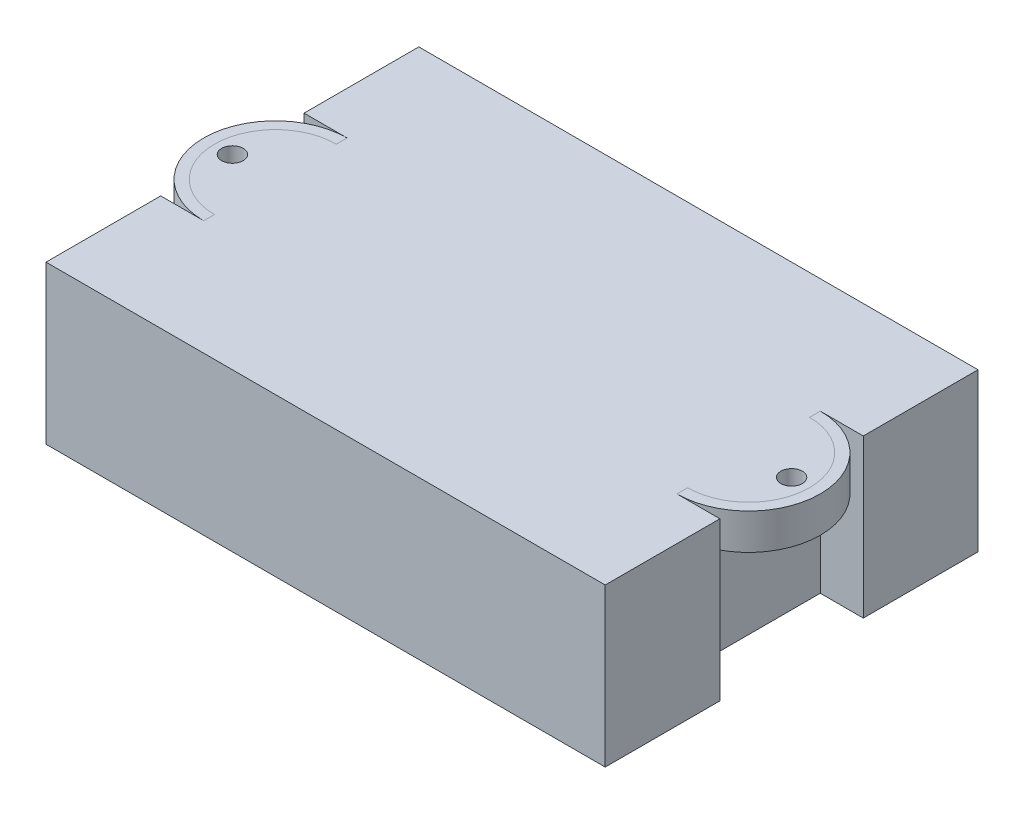
SolidWorks part; units mm, degrees
ref_plane "Piano frontale" through (0, 0, 0) normal (0, 0, 1) x (1, 0, 0)
ref_plane "Piano superiore" through (0, 0, 0) normal (0, 1, 0) x (1, 0, 0)
ref_plane "Piano destro" through (0, 0, 0) normal (1, 0, 0) x (0, 0, -1)
sketch "Schizzo1" plane through (0, 0, 0) normal (0, 1, 0) x (1, 0, 0)
  line L1 (-39, 26) -> (39, 26)
  line L2 (-39, 26) -> (-39, -26)
  line L3 (-39, -26) -> (39, -26)
  line L4 (39, 26) -> (39, -26)
  line L5 (-39, 26) -> (39, -26) construction
  line L6 (-39, -26) -> (39, 26) construction
  point P0 (0, 0)
  dimension "D1" = 52
  dimension "D2" = 78
extrude "Estrusione-Estrusione1" add sketch "Schizzo1" along normal blind 22
sketch "Schizzo3" plane through (0, 22, 0) normal (0, 1, 0) x (1, 0, 0)
  line L0 (0, 31.6789) -> (0, -29.6331) construction
  line L1 (-39, 10) -> (-33, 10)
  line L2 (-39, 26) -> (-39, -26) construction
  line L3 (-33, 10) -> (-33, -10)
  line L4 (-33, -10) -> (-39, -10)
  line L5 (-39, -10) -> (-39, 10)
  line L6 (33, -10) -> (39, -10)
  line L7 (33, 10) -> (33, -10)
  line L8 (39, 10) -> (33, 10)
  line L9 (39, -10) -> (39, 10)
  point P7 (-33, 0)
  dimension "D1" = 20
  dimension "D2" = 6
extrude "Taglio-Estrusione1" cut sketch "Schizzo3" against normal through all
sketch "Schizzo4" plane through (0, 22, 0) normal (0, 1, 0) x (1, 0, 0)
  line L0 (-33, 10) -> (-33, -10)
  line L1 (-33, 8.5) -> (-33, -8.5)
  line L2 (0, 33.3303) -> (0, -35.9371) construction
  line L3 (33, 8.5) -> (33, -8.5)
  line L4 (-39, 26) -> (-39, 10) construction
  line L5 (-39, 14.019) -> (-39, -18) construction
  line L6 (-39, -10) -> (-39, -26) construction
  arc A0 (-33, 10) -> (-33, -10) centre (-33, 0) ccw
  arc A1 (-33, 8.5) -> (-33, -8.5) centre (-33, 0) ccw
  circle A2 centre (-39, 0) radius 1.5
  circle A3 centre (39, 0) radius 1.5
  arc A4 (33, 10) -> (33, -10) centre (33, 0) cw
  arc A5 (33, 8.5) -> (33, -8.5) centre (33, 0) cw
  line M7 (-33, 10) -> (-33, -10)
  line M13 (33, -10) -> (33, 10)
  dimension "D1" = 1.5
  dimension "D2" = 3
extrude "Estrusione-Estrusione2" add sketch "Schizzo4" against normal blind 4 contours A5 A3 M13 | L0 A1 A2 region at (-36.4486, 22, 0) region at (36.4486, 22, 0)
extrude "Estrusione-Estrusione3" add sketch "Schizzo4<3>" against normal blind 5 separate body contours A5 A4 M13 | A1 A0 M7 region at (-33.2236, 22, -9.25) region at (33.2236, 22, -9.25)
sketch "Schizzo4<3>" plane through (0, 22, 0) normal (0, 1, 0) x (1, 0, 0) same geometry as "Schizzo4"
